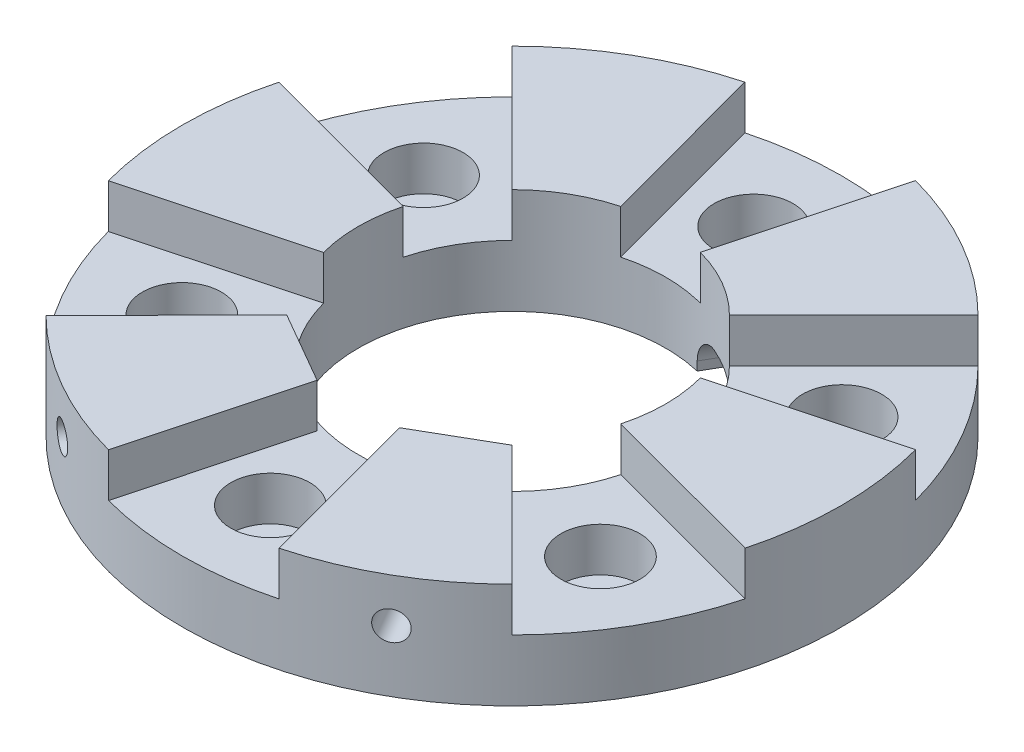
SolidWorks part; units mm, degrees
ref_plane "Front" through (0, 0, 0) normal (0, 0, 1) x (1, 0, 0)
ref_plane "Top" through (0, 0, 0) normal (0, 1, 0) x (1, 0, 0)
ref_plane "Right" through (0, 0, 0) normal (1, 0, 0) x (0, 0, -1)
sketch "Sketch1" plane through (0, 0, 0) normal (0, 1, 0) x (1, 0, 0)
  circle A0 centre (0, 0) radius 37.5
  circle A1 centre (0, 27.5) radius 2.3
  circle A2 centre (23.8157, 13.75) radius 2.3
  circle A3 centre (23.8157, -13.75) radius 2.3
  circle A4 centre (0, -27.5) radius 2.3
  circle A5 centre (-23.8157, -13.75) radius 2.3
  circle A6 centre (-23.8157, 13.75) radius 2.3
  point P17 (0, 0)
  dimension "D1" = 75
  dimension "D2" = 4.6
  dimension "D3" = 27.5
  dimension "D5" = 13.75
  dimension "D6" = 23.8157
  dimension "D7" = 23.8157
  dimension "D4" = 6
extrude "Boss-Extrude1" add sketch "Sketch1" along normal blind 2
sketch "Sketch2" plane through (0, 2, 0) normal (0, 1, 0) x (1, 0, 0)
  circle A0 centre (0, 0) radius 37.5
  circle A1 centre (0, -27.5) radius 2.3 construction
  circle A2 centre (0, -27.5) radius 2.3
  circle A3 centre (-23.8157, 13.75) radius 2.3 construction
  circle A4 centre (-23.8157, -13.75) radius 2.3 construction
  circle A5 centre (23.8157, -13.75) radius 2.3 construction
  circle A6 centre (23.8157, 13.75) radius 2.3 construction
  circle A7 centre (0, 27.5) radius 2.3 construction
  circle A8 centre (-23.8157, 13.75) radius 2.3
  circle A9 centre (-23.8157, -13.75) radius 2.3
  circle A10 centre (23.8157, -13.75) radius 2.3
  circle A11 centre (23.8157, 13.75) radius 2.3
  circle A12 centre (0, 27.5) radius 2.3
  circle A13 centre (0, 27.5) radius 4.5
  circle A14 centre (23.8157, 13.75) radius 4.5
  circle A15 centre (23.8157, -13.75) radius 4.5
  circle A16 centre (0, -27.5) radius 4.5
  circle A17 centre (-23.8157, -13.75) radius 4.5
  circle A18 centre (-23.8157, 13.75) radius 4.5
  point P34 (0, 0)
  circle M10 centre (0, 0) radius 37.5
  dimension "D1" = 9
  dimension "D3" = 75
  dimension "D2" = 6
extrude "Boss-Extrude2" add sketch "Sketch2" along normal blind 5 contours A18 A17 A16 A15 A14 A13 M10 region at (0, 2, 0)
sketch "Sketch3" plane through (0, 7, 0) normal (0, 1, 0) x (1, 0, 0)
  line L0 (-23.8157, 13.75) -> (-15.1554, 8.75)
  line L1 (-23.8157, 13.75) -> (-32.476, 18.75)
  line L2 (0, 0) -> (-36.2261, 9.6913)
  line L3 (0, 0) -> (-36.2184, -9.7201)
  line L4 (0, 0) -> (-9.7201, 36.2184)
  line L5 (0, 0) -> (-26.5271, 26.506)
  line L6 (0, 0) -> (26.506, 26.5271)
  line L7 (0, 0) -> (9.6913, 36.2261)
  line L8 (0, 0) -> (36.2261, -9.6913)
  line L9 (0, 0) -> (36.2184, 9.7201)
  line L10 (0, 0) -> (9.7201, -36.2184)
  line L11 (0, 0) -> (26.5271, -26.506)
  line L12 (0, 0) -> (-26.506, -26.5271)
  line L13 (0, 0) -> (-9.6913, -36.2261)
  line L14 (-12.8058, -12.816) -> (-4.6821, -17.5019)
  line L15 (-12.8058, -12.816) -> (-12.3694, -12.3793)
  line L16 (-4.6821, -17.5019) -> (-4.5226, -16.9055)
  line L17 (4.6947, -17.4931) -> (12.8197, -12.8095)
  line L20 (0, 0) -> (0, 37.5)
  circle A0 centre (0, 0) radius 37.5
  circle A1 centre (0, 0) radius 17.5
  point P22 (0, 0)
  circle M7 centre (0, 0) radius 37.5
  dimension "D1" = 75
  dimension "D2" = 6
  dimension "D5" = 30
extrude "Boss-Extrude3" add sketch "Sketch3" along normal blind 5 contours A1 L2 L3 M7 | A1 L4 L5 M7 | A1 L6 L7 M7 | A1 L8 L9 M7 | A1 L10 L11 M7 | A1 L12 L13 M7 region at (-14.2024, 7, -24.5767) region at (-28.3853, 7, 0.0113) region at (14.1828, 7, -24.588) region at (28.3853, 7, -0.0113) region at (-14.2192, 7, 24.6511) region at (14.2386, 7, 24.6399)
sketch "Sketch4" plane through (0, 7, 0) normal (0, 1, 0) x (1, 0, 0)
  circle A0 centre (0, 0) radius 17.5
extrude "Cut-Extrude1" cut sketch "Sketch4" against normal blind 7
sketch "Sketch5" plane through (-8.744, 0, 15.1589) normal (0.4997, 0, -0.8662) x (-0.8662, 0, -0.4997)
  line L0 (4.6891, 12) -> (-4.6891, 12) construction
  line L1 (3.2909, 7) -> (1.6454, 9.85)
  line L2 (1.6454, 9.85) -> (-1.6454, 9.85)
  line L3 (-1.6454, 9.85) -> (-3.2909, 7)
  line L4 (-3.2909, 7) -> (-1.6454, 4.15)
  line L5 (-1.6454, 4.15) -> (1.6454, 4.15)
  line L6 (1.6454, 4.15) -> (3.2909, 7)
  line L7 (0, 7) -> (4.6891, 7)
  line L8 (4.6891, 12) -> (4.6891, 7) construction
  line L9 (0, 7) -> (-4.6891, 7)
  line L10 (-4.6891, 12) -> (-4.6891, 7) construction
  circle A0 centre (0, 7) radius 1.5
  circle A1 centre (0, 7) radius 2.85 construction
  point P2 (0, 12)
  line M2 (0, 7) -> (4.6891, 7)
  line M6 (-4.6891, 7) -> (0, 7)
  dimension "D1" = 3
  dimension "D3" = 5.7
  dimension "D2" = 5
extrude "Cut-Extrude2" cut sketch "Sketch5" against normal blind 2.5 and the other way blind 7 contours A0 L7 L1 L2 L3 M6 | A0 L4 L5 L6 L7 M6 | A0 L9 M2 | L9 A0 M2 region at (-10.819, 7.0717, 13.962) region at (-10.8282, 5.6109, 13.9567) region at (-8.744, 6.3634, 15.1589) region at (-8.744, 7.6366, 15.1589)
sketch "Sketch7" plane through (8.7396, 0, 15.1614) normal (-0.4994, 0, -0.8664) x (-0.8664, 0, 0.4994)
  line L0 (4.6688, 12) -> (-4.7094, 12) construction
  line L1 (3.2706, 7) -> (1.6252, 9.85)
  line L2 (1.6252, 9.85) -> (-1.6657, 9.85)
  line L3 (-1.6657, 9.85) -> (-3.3112, 7)
  line L4 (-3.3112, 7) -> (-1.6657, 4.15)
  line L5 (-1.6657, 4.15) -> (1.6252, 4.15)
  line L6 (1.6252, 4.15) -> (3.2706, 7)
  line L7 (-0.0203, 7) -> (4.6688, 7)
  line L8 (-0.0203, 7) -> (-4.7094, 7)
  line L9 (-4.7094, 12) -> (-4.7094, 7) construction
  line L10 (4.6688, 12) -> (4.6688, 7) construction
  circle A0 centre (-0.0203, 7) radius 2.85 construction
  line M7 (0, 7) -> (4.6688, 7)
  line M11 (-4.7094, 7) -> (0, 7)
  dimension "D1" = 5.7
  dimension "D2" = 5
extrude "Cut-Extrude4" cut sketch "Sketch7" against normal blind 2.5 and the other way blind 3 contours L2 L3 L1 M11 M7 | L5 L6 L4 M7 M11 region at (8.7572, 8.2667, 15.1513) region at (8.7572, 5.7333, 15.1513)
sketch "Sketch10" plane through (8.7396, 0, 15.1614) normal (-0.4994, 0, -0.8664) x (-0.8664, 0, 0.4994)
  line L0 (1.6252, 4.15) -> (3.2706, 7) construction
  line L1 (-1.6657, 4.15) -> (1.6252, 4.15) construction
  line L2 (4.6688, 12) -> (-4.7094, 12) construction
  circle A0 centre (-0.0203, 7) radius 1.65
  point P6 (-0.0203, 12)
  dimension "D1" = 3.3
  dimension "D2" = 2.85
  dimension "D3" = 2.85
  dimension "D4" = 5
extrude "Cut-Extrude7" cut sketch "Sketch10" against normal blind 20
sketch "Sketch9" plane through (-9.9931, 0, 17.3245) normal (0.4997, 0, -0.8662) x (-0.8662, 0, -0.4997)
  line L0 (-1.6454, 4.15) -> (1.6454, 4.15) construction
  circle A0 centre (0, 6.9) radius 1.65
  point P2 (0, 4.15)
  dimension "D1" = 3.3
  dimension "D2" = 2.75
extrude "Cut-Extrude6" cut sketch "Sketch9" against normal blind 20
sketch "Sketch14" plane through (0, 0, 0) normal (0, -1, 0) x (1, 0, 0)
  line L0 (14.2525, -34.686) -> (4.0551, -17.0237)
  line L1 (22.9127, -29.686) -> (12.7154, -12.0237)
  line L2 (0, 0) -> (0, -37.5)
  line L3 (0, 0) -> (18.75, -32.476)
  circle A2 centre (0, 0) radius 17.5
  circle A3 centre (0, 0) radius 37.5
  circle M1 centre (0, 0) radius 17.5
  circle M5 centre (0, 0) radius 37.5
  dimension "D2" = 75
  dimension "D3" = 35
  dimension "D1" = 30
  dimension "D4" = 5
  dimension "D5" = 5
extrude "Cut-Extrude8" cut sketch "Sketch14" against normal blind 4 contours L3 L1 M1 M5 | L3 L0 M1 M5 region at (11.4893, 0, -24.9163) region at (15.8335, 0, -22.4082)
fillet "Fillet1" radius 3 2 edges at (17.814, 4, -20.8548) (9.1538, 4, -25.8548)
